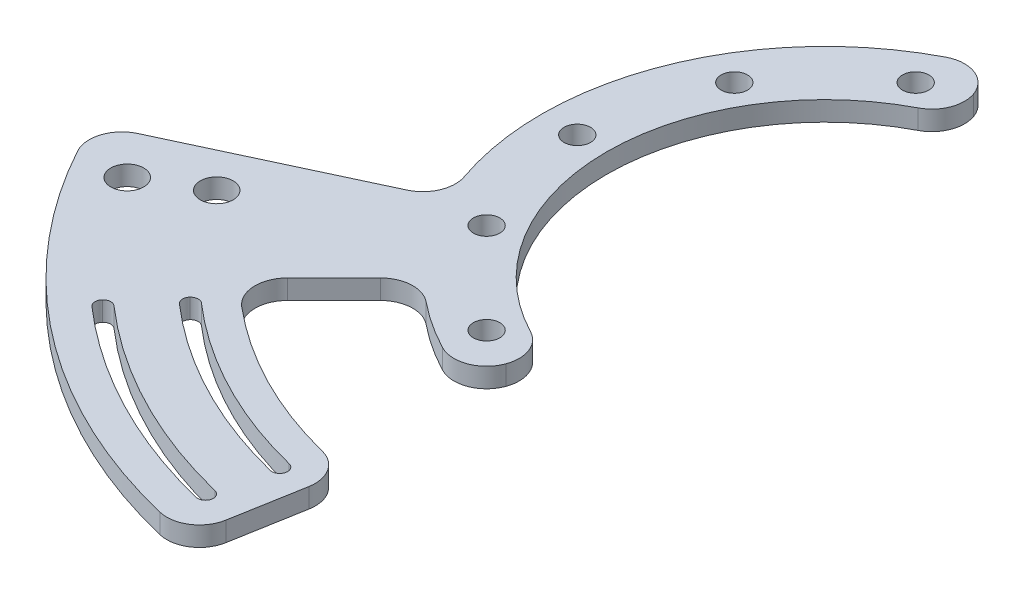
SolidWorks part; units mm, degrees
ref_plane "Front Plane" through (0, 0, 0) normal (0, 0, 1) x (1, 0, 0)
ref_plane "Top Plane" through (0, 0, 0) normal (0, 1, 0) x (1, 0, 0)
ref_plane "Right Plane" through (0, 0, 0) normal (1, 0, 0) x (0, 0, -1)
sketch "Sketch1" plane through (0, 0, 0) normal (0, 1, 0) x (1, 0, 0)
  circle A0 centre (0, 0) radius 38 construction
  circle A1 centre (0, 0) radius 43.5
  circle A2 centre (0, 0) radius 33.5
  dimension "D1" = 76
  dimension "D2" = 67
  dimension "D3" = 87
extrude "Boss-Extrude1" add sketch "Sketch1" along normal blind 3
sketch "Sketch3" plane through (0, 3, 0) normal (0, 1, 0) x (1, 0, 0)
  line L0 (0, 0) -> (-38, 0) construction
  circle A0 centre (-38, 0) radius 2.025
  dimension "D1" = 4.05
  dimension "D2" = 38
extrude "Cut-Extrude2" cut sketch "Sketch3" against normal through all both and the other way through all
pattern_circular "CirPattern1" count 12 over 360 about axis through (0, 3, 0) along (0, 1, 0) of "Cut-Extrude2"
sketch "Sketch2" plane through (0, 3, 0) normal (0, 1, 0) x (1, 0, 0)
  line L0 (0, 0) -> (43.5, 0)
  line L1 (0, 0) -> (-14.8779, -40.8766)
  circle A0 centre (0, 0) radius 43.5 construction
  arc A1 (-14.8779, -40.8766) -> (43.5, 0) centre (0, 0) ccw
  dimension "D1" = 110
extrude "Cut-Extrude1" cut sketch "Sketch2" against normal through all both and the other way through all
mirror "Mirror1" about plane through (0, 0, 0) normal (0, 0, 1) of "Cut-Extrude1"
sketch "Sketch4" plane through (0, 0, 0) normal (0, 1, 0) x (1, 0, 0)
  line L0 (0, 0) -> (-43.5, 0) construction
  line L1 (0, 0) -> (-76.583, -35.7112)
  line L2 (-14.6733, -83.2163) -> (-11.0267, -62.5353)
  line L3 (-57.5505, -26.8363) -> (-76.583, -35.7112)
  line L4 (-44.9013, -44.9013) -> (-30.7591, -30.7591)
  arc A0 (-14.8779, 40.8766) -> (-14.8779, -40.8766) centre (0, 0) ccw construction
  arc A1 (-76.583, -35.7112) -> (-14.6733, -83.2163) centre (0, 0) ccw
  arc A2 (-11.0267, -62.5353) -> (-57.5505, -26.8363) centre (0, 0) cw construction
  arc A3 (-11.0267, -62.5353) -> (-44.9013, -44.9013) centre (0, 0) cw
  arc A4 (-30.7591, -30.7591) -> (-39.4244, -18.3839) centre (0, 0) cw
  dimension "D5" = 45
  dimension "D1" = 21
  dimension "D2" = 63.5
  dimension "D3" = 25
  dimension "D4" = 80
extrude "Boss-Extrude2" add sketch "Sketch4" along normal up to surface (3 mm away) contours L4 L1 A1 L2 region at (-43.7257, 0, 51.6581) up to face at (-38, 3, 2.025)
sketch "Sketch5" plane through (0, 3, 0) normal (0, 1, 0) x (1, 0, 0)
  line L0 (-17.6587, -76.4881) -> (-15.5216, -67.2315) construction
  line L1 (-52.5268, -58.3369) -> (-46.17, -51.277) construction
  line L2 (-14.6733, -83.2163) -> (-11.0267, -62.5353) construction
  line L3 (-39.4244, -18.3839) -> (-76.583, -35.7112) construction
  arc A0 (-46.17, -51.277) -> (-15.5216, -67.2315) centre (0, 0) ccw
  arc A1 (-52.5268, -58.3369) -> (-17.6587, -76.4881) centre (0, 0) ccw
  arc A2 (-44.9013, -44.9013) -> (-11.0267, -62.5353) centre (0, 0) ccw construction
  dimension "D4" = 5.5
  dimension "D1" = 9.5
  dimension "D2" = 3
  dimension "D3" = 23
extrude "Cut-Extrude-Thin1" cut sketch "Sketch5" against normal blind 3 thin thin type mid plane wall 2.4
fillet "Fillet1" radius 1.2 8 edges at (-46.973, 1.5, 52.1688) (-53.3297, 1.5, 59.2286) (-45.3671, 1.5, 50.3852) (-51.7238, 1.5, 57.4451) (-15.2517, 1.5, 66.0623) (-17.3887, 1.5, 75.3188) (-15.7916, 1.5, 68.4008) (-17.9286, 1.5, 77.6573)
fillet "Fillet2" radius 5 10 edges at (-11.4577, 1.5, -31.4797) (-11.4577, 1.5, 31.4797) (-39.4244, 1.5, 18.3839) (-76.583, 1.5, 35.7112) (-14.6733, 1.5, 83.2163) (-11.0267, 1.5, 62.5353) (-30.7591, 1.5, 30.7591) (-44.9013, 1.5, 44.9013)
sketch "Sketch6" plane through (0, 3, 0) normal (0, 1, 0) x (1, 0, 0)
  line L0 (0, 0) -> (-72.4306, -43.5207) construction
  line L1 (-43.7217, -20.3878) -> (-71.9088, -33.5316) construction
  arc A0 (-74.1854, -40.4571) -> (-19.8779, -82.1287) centre (0, 0) ccw construction
  circle A1 centre (-58.2874, -35.0226) radius 2.525
  circle A2 centre (-66.859, -40.173) radius 2.525
  dimension "D1" = 5.05
  dimension "D2" = 10
  dimension "D3" = 78
  dimension "D4" = 6
extrude "Cut-Extrude3" cut sketch "Sketch6" against normal through all both and the other way through all
sketch "Sketch7" plane through (0, 0, 0) normal (0, 1, 0) x (1, 0, 0)
  line L0 (0, 0) -> (-58.9789, 41.2975) construction
  line L1 (-58.9789, 41.2975) -> (-35.6331, 24.9506)
  line L2 (0, 0) -> (-43.5, 0) construction
  line L3 (-58.9789, 31.2975) -> (-39.6941, 17.7941)
  line L5 (-58.9789, 41.2975) -> (-58.9789, 31.2975)
  line L8 (-58.9789, 41.2975) -> (-73.9789, 41.2975)
  line L9 (-58.9789, 41.2975) -> (-58.9789, 31.2975)
  line L10 (-73.9789, 41.2975) -> (-73.9789, 31.2975)
  line L11 (-58.9789, 31.2975) -> (-73.9789, 31.2975)
  arc A0 (-20.0605, 38.5983) -> (-41.1096, -14.2216) centre (0, 0) ccw construction
  arc A1 (-39.6941, 17.7941) -> (-35.6331, 24.9506) centre (0, 0) cw
  dimension "D1" = 72
  dimension "D2" = 35
  dimension "D3" = 10
  dimension "D4" = 15
extrude "Boss-Extrude3" [suppressed] add sketch "Sketch7" along normal up to surface (3 mm away) up to face at (-58.2874, 3, 37.5476)
sketch "Sketch9" [suppressed] plane through (0, 3, 0) normal (0, 1, 0) x (1, 0, 0)
  line L0 (-73.9789, 37.2975) -> (-53.2664, 37.2975) construction
  line L1 (-73.9789, 41.2975) -> (-73.9789, 31.2975) construction
  line L2 (-58.9789, 41.2975) -> (-35.6331, 24.9506) construction
  line L3 (-58.9789, 41.2975) -> (-73.9789, 41.2975) construction
  circle A0 centre (-69.9789, 37.2975) radius 1.2
  circle A1 centre (-60.4789, 37.2975) radius 1.2
  dimension "D1" = 2.4
  dimension "D2" = 9.5
  dimension "D3" = 4
  dimension "D4" = 4
extrude "Cut-Extrude5" [suppressed] cut sketch "Sketch9" against normal through all both and the other way through all
